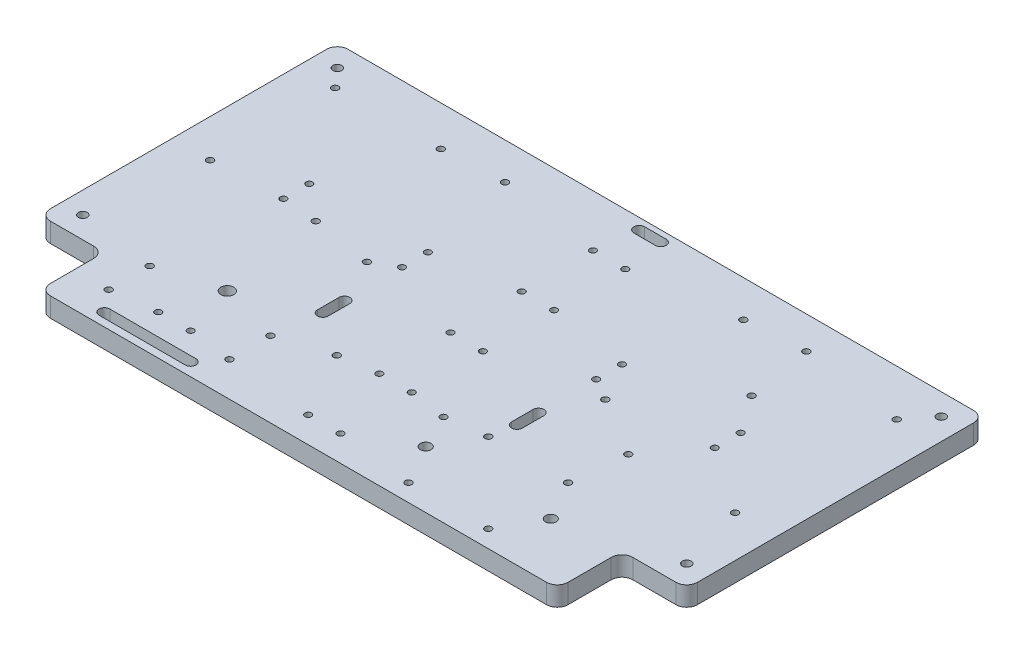
SolidWorks part; units mm, degrees
ref_plane "Plan de face" through (0, 0, 0) normal (0, 0, 1) x (1, 0, 0)
ref_plane "Plan de dessus" through (0, 0, 0) normal (0, 1, 0) x (1, 0, 0)
ref_plane "Plan de droite" through (0, 0, 0) normal (1, 0, 0) x (0, 0, -1)
sketch "Esquisse1" plane through (0, 0, 0) normal (0, 1, 0) x (1, 0, 0)
  line L0 (0, 81.3484) -> (0, -60.6791) construction
  line L1 (-137.8937, 0) -> (185.4331, 0) construction
  line L4 (150, -69) -> (150, 69)
  line L6 (-150, -69) -> (-150, 69)
  line L7 (150, -69) -> (-150, 69) construction
  line L8 (150, 69) -> (-150, -69) construction
  line L13 (80, -48.6) -> (80, 59) construction
  line L18 (-149.8488, 69) -> (-150, 69)
  line L22 (80, 59) -> (133.34, 59) construction
  line L23 (133.34, 59) -> (133.34, -48.6) construction
  line L24 (-104, -64) -> (-48, -64) construction
  line L25 (-104, -64) -> (-104, -83) construction
  line L26 (-104, -83) -> (-48, -83) construction
  line L27 (-48, -64) -> (-48, -83) construction
  line L28 (-104, -64) -> (-48, -83) construction
  line L29 (-104, -83) -> (-48, -64) construction
  line L35 (-132.5, 50.5) -> (-83.5, 50.5) construction
  line L40 (-76, -86) -> (-76, -93) construction
  line L46 (-56, -93) -> (-96, -93) construction
  line L47 (-56, -95.5) -> (-96, -95.5)
  line L53 (133.34, -48.6) -> (80, -48.6) construction
  line L54 (-136, 54) -> (-80, 54) construction
  line L55 (-136, 54) -> (-136, -34) construction
  line L56 (-136, -34) -> (-80, -34) construction
  line L57 (-80, 54) -> (-80, -34) construction
  line L58 (-136, 54) -> (-80, -34) construction
  line L59 (-136, -34) -> (-80, 54) construction
  line L60 (-107, -61) -> (-45, -61) construction
  line L61 (-107, -61) -> (-107, -86) construction
  line L62 (-107, -86) -> (-45, -86) construction
  line L63 (-45, -61) -> (-45, -86) construction
  line L64 (-107, -61) -> (-45, -86) construction
  line L65 (-107, -86) -> (-45, -61) construction
  line L66 (82.54, -48.6) -> (82.54, 59) construction
  line L67 (130.8, -48.6) -> (130.8, 59) construction
  line L68 (80, -42.6) -> (133.34, -42.6) construction
  line L69 (87.62, 23.44) -> (87.62, 59) construction
  line L71 (-120, -99) -> (120, -99)
  line L72 (120, -99) -> (120, -69)
  line L73 (-149.8488, 69) -> (150, 69)
  line L75 (120, -69) -> (150, -69)
  line L76 (-150, -69) -> (150, -69) construction
  line L77 (-150, -69) -> (-120, -69)
  line L78 (-120, -69) -> (-120, -99)
  line L79 (-63.25, 59) -> (-63.25, -19) construction
  line L80 (-63.25, -19) -> (-29.75, -19) construction
  line L81 (-29.75, -19) -> (-29.75, -61.5) construction
  line L82 (-29.75, -61.5) -> (29.75, -61.5) construction
  line L83 (29.75, -61.5) -> (29.75, -19) construction
  line L84 (29.75, -19) -> (63.25, -19) construction
  line L85 (63.25, -19) -> (63.25, 59) construction
  line L86 (63.25, 59) -> (-63.25, 59) construction
  line L87 (-83.5, 50.5) -> (-83.5, -7.5) construction
  line L88 (43, -54) -> (80, -54) construction
  line L89 (43, -54) -> (43, -91) construction
  line L90 (43, -91) -> (80, -91) construction
  line L91 (80, -54) -> (80, -91) construction
  line L92 (43, -54) -> (80, -91) construction
  line L93 (43, -91) -> (80, -54) construction
  line L94 (40, -51) -> (83, -51) construction
  line L95 (40, -51) -> (40, -94) construction
  line L96 (40, -94) -> (83, -94) construction
  line L97 (83, -51) -> (83, -94) construction
  line L98 (40, -51) -> (83, -94) construction
  line L99 (40, -94) -> (83, -51) construction
  line L100 (-83.5, -7.5) -> (-132.5, -7.5) construction
  line L101 (-132.5, -7.5) -> (-132.5, 50.5) construction
  line L102 (-108, 54) -> (-108, -34) construction
  line L103 (0, -61.5) -> (0, 59) construction
  line L104 (-63.25, 20) -> (63.25, 20) construction
  line L105 (-55.25, 52) -> (55.25, 52) construction
  line L106 (-55.25, 52) -> (-55.25, -12) construction
  line L107 (-55.25, -12) -> (55.25, -12) construction
  line L108 (55.25, 52) -> (55.25, -12) construction
  line L109 (-55.25, 52) -> (55.25, -12) construction
  line L110 (-55.25, -12) -> (55.25, 52) construction
  line L111 (-29.75, -56.5) -> (29.75, -56.5) construction
  line L112 (-56, -90.5) -> (-96, -90.5)
  line L113 (32.5, -72.5) -> (90.5, -72.5) construction
  line L114 (-5, 64) -> (5, 64) construction
  line L115 (-5, 66.5) -> (5, 66.5)
  line L116 (-5, 61.5) -> (5, 61.5)
  line L117 (-45, -37.7091) -> (48.5817, -37.7091) construction
  line L118 (-45, -32.7091) -> (-45, -42.7091) construction
  line L119 (-42.5, -32.7091) -> (-42.5, -42.7091)
  line L120 (-47.5, -32.7091) -> (-47.5, -42.7091)
  line L121 (45, -32.7091) -> (45, -42.7091) construction
  line L122 (42.5, -32.7091) -> (42.5, -42.7091)
  line L123 (47.5, -32.7091) -> (47.5, -42.7091)
  line L124 (-76, -61) -> (-76, -56) construction
  circle A0 centre (-140, 59) radius 2.05
  circle A1 centre (140, 59) radius 2.05
  circle A2 centre (140, -59) radius 2.05
  circle A3 centre (-140, -59) radius 2.05
  circle A19 centre (-48, -83) radius 1.55
  circle A20 centre (-104, -83) radius 1.55
  circle A21 centre (-48, -64) radius 1.55
  circle A22 centre (-104, -64) radius 1.55
  circle A27 centre (82.54, -28.63) radius 1.55
  circle A28 centre (130.8, -27.36) radius 1.55
  circle A29 centre (130.8, 47.57) radius 1.55
  circle A30 centre (82.54, 53.92) radius 1.55
  circle A31 centre (87.62, 23.44) radius 1.55
  circle A32 centre (43, -54) radius 1.55
  circle A33 centre (80, -54) radius 1.55
  circle A34 centre (80, -91) radius 1.55
  circle A35 centre (43, -91) radius 1.55
  circle A36 centre (-132.5, 50.5) radius 1.55
  circle A37 centre (-132.5, -7.5) radius 1.55
  circle A38 centre (-83.5, -7.5) radius 1.55
  circle A39 centre (-83.5, 50.5) radius 1.55
  circle A40 centre (-55.25, 52) radius 1.55
  circle A41 centre (-55.25, -12) radius 1.55
  circle A42 centre (55.25, 52) radius 1.55
  circle A43 centre (55.25, -12) radius 1.55
  circle A44 centre (-24.75, -56.5) radius 1.55
  circle A45 centre (24.75, -56.5) radius 1.55
  arc A46 (-56, -95.5) -> (-56, -90.5) centre (-56, -93) ccw
  arc A47 (-96, -90.5) -> (-96, -95.5) centre (-96, -93) ccw
  circle A48 centre (32.5, -72.5) radius 2.5
  circle A49 centre (90.5, -72.5) radius 2.5
  arc A50 (-5, 66.5) -> (-5, 61.5) centre (-5, 64) ccw
  arc A51 (5, 61.5) -> (5, 66.5) centre (5, 64) ccw
  arc A52 (-42.5, -32.7091) -> (-47.5, -32.7091) centre (-45, -32.7091) ccw
  arc A53 (-47.5, -42.7091) -> (-42.5, -42.7091) centre (-45, -42.7091) ccw
  arc A54 (42.5, -32.7091) -> (47.5, -32.7091) centre (45, -32.7091) cw
  arc A55 (47.5, -42.7091) -> (42.5, -42.7091) centre (45, -42.7091) cw
  circle A56 centre (-76, -56) radius 3
  point P1 (0, 0)
  point P21 (-76, -73.5)
  point P35 (0, 100)
  point P45 (-76, -93)
  point P61 (-76, -73.5)
  point P95 (61.5, -72.5)
  point P102 (61.5, -72.5)
  point P111 (40, -72.5)
  point P114 (0, 20)
  point P131 (0, 64)
  point P140 (-45, -37.7091)
  point P147 (45, -37.7091)
  dimension "D5" = 4.1
  dimension "D6" = 130
  dimension "D7" = 138
  dimension "D8" = 140
  dimension "D11" = 10
  dimension "D9" = 10
  dimension "D13" = 7.5
  dimension "D19" = 50.8
  dimension "D20" = 3.1
  dimension "D25" = 7.62
  dimension "D41" = 3.1
  dimension "D48" = 3.1
  dimension "D59" = 3.1
  dimension "D60" = 49.5
  dimension "D62" = 5
  dimension "D69" = 6
  dimension "D4" = 150
  dimension "D10" = 5
  dimension "D12" = 40
  dimension "D14" = 6
  dimension "D15" = 10
  dimension "D16" = 101.6
  dimension "D17" = 53.34
  dimension "D18" = 2.54
  dimension "D21" = 96.52
  dimension "D22" = 90.17
  dimension "D23" = 13.97
  dimension "D24" = 15.24
  dimension "D26" = 66.04
  dimension "D27" = 3
  dimension "D28" = 3
  dimension "D29" = 25
  dimension "D30" = 62
  dimension "D31" = 10
  dimension "D32" = 30
  dimension "D33" = 30
  dimension "D34" = 45
  dimension "D35" = 80
  dimension "D36" = 7.5
  dimension "D37" = 43
  dimension "D38" = 43
  dimension "D39" = 3
  dimension "D40" = 3
  dimension "D42" = 40
  dimension "D43" = 120
  dimension "D44" = 88
  dimension "D45" = 56
  dimension "D46" = 3.5
  dimension "D47" = 58
  dimension "D49" = 49
  dimension "D50" = 3.5
  dimension "D51" = 15
  dimension "D52" = 80
  dimension "D53" = 126.5
  dimension "D54" = 59.5
  dimension "D55" = 78
  dimension "D56" = 42.5
  dimension "D57" = 64
  dimension "D58" = 110.5
  dimension "D61" = 44.5
  dimension "D63" = 5
  dimension "D64" = 5
  dimension "D65" = 10
  dimension "D66" = 10
  dimension "D67" = 5
  dimension "D68" = 45
  dimension "D70" = 5
extrude "Boss.-Extru.1" add sketch "Esquisse1" along normal blind 9
fillet "Congé2" radius 5 8 edges at (150, 4.5, -69) (-150, 4.5, -69) (-150, 4.5, 69) (150, 4.5, 69) (120, 4.5, 69) (120, 4.5, 99) (-120, 4.5, 69) (-120, 4.5, 99)
sketch "Esquisse2" plane through (0, 9, 0) normal (0, 1, 0) x (1, 0, 0)
  line L0 (0, 69) -> (0, -99) construction
  line L1 (-150, 0) -> (150, 0) construction
  line L2 (0, 46.3302) -> (0, 45) construction
  line L3 (0, 45) -> (-7.5, 45) construction
  line L4 (-76, -90.5) -> (-76, -75) construction
  line L5 (-56, -90.5) -> (-96, -90.5) construction
  line L8 (150, -64) -> (150, 64)
  line L9 (145, 69) -> (-145, 69)
  line L10 (-150, 64) -> (-150, -64)
  line L11 (-145, -69) -> (-125, -69)
  line L12 (-120, -74) -> (-120, -94)
  line L13 (-115, -99) -> (115, -99)
  line L14 (120, -94) -> (120, -74)
  line L15 (125, -69) -> (145, -69)
  line L16 (150, -64) -> (150, 64)
  line L17 (145, 69) -> (-145, 69)
  line L18 (-150, 64) -> (-150, -64)
  line L19 (-145, -69) -> (-125, -69)
  line L20 (-120, -74) -> (-120, -94)
  line L21 (-115, -99) -> (115, -99)
  line L22 (120, -94) -> (120, -74)
  line L23 (125, -69) -> (145, -69)
  circle A0 centre (-7.5, 45) radius 1.5
  circle A1 centre (7.5, 45) radius 1.5
  circle A2 centre (-7.5, 12) radius 1.5
  circle A3 centre (7.5, 12) radius 1.5
  circle A4 centre (-7.5, -21) radius 1.5
  circle A5 centre (7.5, -21) radius 1.5
  circle A6 centre (-7.5, -54) radius 1.5
  circle A7 centre (7.5, -54) radius 1.5
  arc A8 (150, 64) -> (145, 69) centre (145, 64) ccw
  arc A9 (-145, 69) -> (-150, 64) centre (-145, 64) ccw
  arc A10 (-150, -64) -> (-145, -69) centre (-145, -64) ccw
  arc A11 (-120, -74) -> (-125, -69) centre (-125, -74) ccw
  arc A12 (-120, -94) -> (-115, -99) centre (-115, -94) ccw
  arc A13 (115, -99) -> (120, -94) centre (115, -94) ccw
  arc A14 (125, -69) -> (120, -74) centre (125, -74) ccw
  arc A15 (145, -69) -> (150, -64) centre (145, -64) ccw
  arc A16 (150, 64) -> (145, 69) centre (145, 64) ccw
  arc A17 (-145, 69) -> (-150, 64) centre (-145, 64) ccw
  arc A18 (-150, -64) -> (-145, -69) centre (-145, -64) ccw
  arc A19 (-120, -74) -> (-125, -69) centre (-125, -74) ccw
  arc A20 (-120, -94) -> (-115, -99) centre (-115, -94) ccw
  arc A21 (115, -99) -> (120, -94) centre (115, -94) ccw
  arc A22 (125, -69) -> (120, -74) centre (125, -74) ccw
  arc A23 (145, -69) -> (150, -64) centre (145, -64) ccw
  circle A24 centre (-7.5, -87) radius 1.5
  circle A25 centre (7.5, -87) radius 1.5
  circle A26 centre (-100, 6) radius 1.5
  circle A27 centre (-100, -6) radius 1.5
  circle A28 centre (100, -6) radius 1.5
  circle A29 centre (100, 6) radius 1.5
  circle A30 centre (-83.5, -80.5) radius 1.5
  circle A31 centre (-68.5, -80.5) radius 1.5
  circle A32 centre (-45, -6) radius 1.5
  circle A33 centre (-45, 6) radius 1.5
  circle A34 centre (45, 6) radius 1.5
  circle A35 centre (45, -6) radius 1.5
  dimension "D2" = 3
  dimension "D6" = 6
  dimension "D7" = 3
  dimension "D10" = 7.5
  dimension "D11" = 3
  dimension "D3" = 7.5
  dimension "D4" = 45
  dimension "D8" = 100
  dimension "D9" = 33
  dimension "D12" = 10
  dimension "D14" = 55
  dimension "D1" = 0
  dimension "D5" = 5
  dimension "D13" = 2
  dimension "D15" = 2
extrude "Enlèv. mat.-Extru.1" cut sketch "Esquisse2" against normal blind 10 contours A0 | A1 | A3 | A2 | A4 | A5 | A6 | A7 | A24 | A25 | A27 | A26 | A28 | A29 | A31 | A30 | A32 | A33 | A35 | A34
